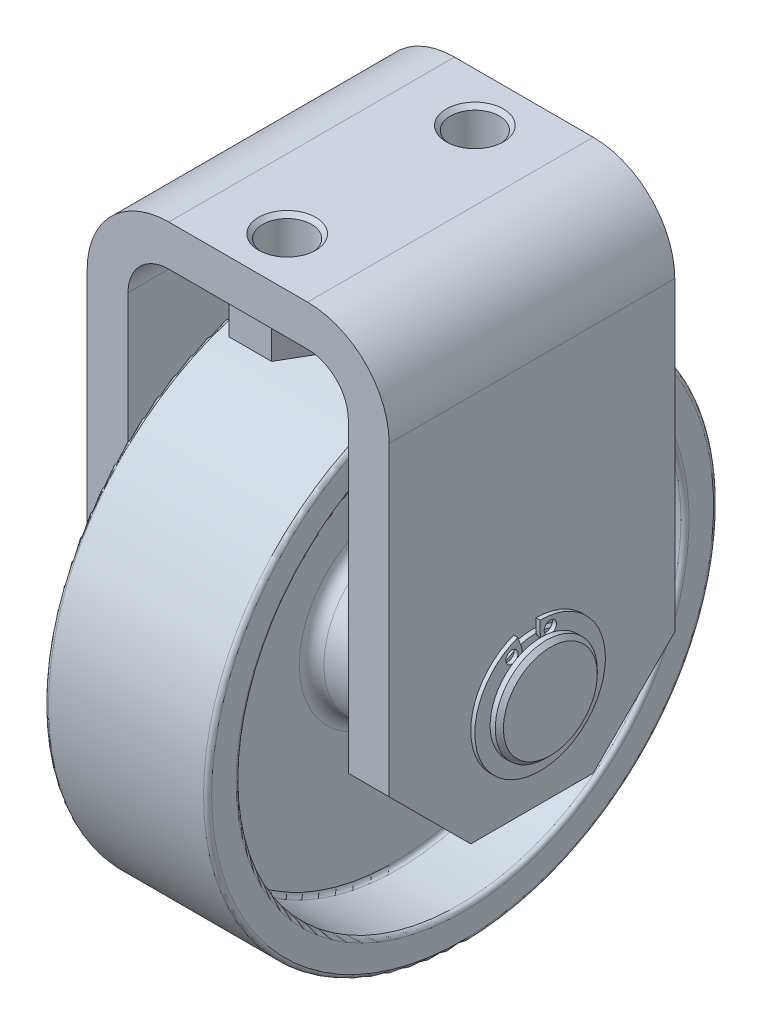
SolidWorks part; units mm, degrees
ref_plane "Front Plane" through (0, 0, 0) normal (0, 0, 1) x (1, 0, 0)
ref_plane "Top Plane" through (0, 0, 0) normal (0, 1, 0) x (1, 0, 0)
ref_plane "Right Plane" through (0, 0, 0) normal (1, 0, 0) x (0, 0, -1)
sketch "Sketch1" plane through (0, 0, 0) normal (0, 0, 1) x (1, 0, 0)
  line L0 (-43.3817, 0) -> (51.6188, 0) construction
  line L1 (55, 0) -> (-55, 0) construction
  line L2 (24, 13) -> (-24, 13)
  line L3 (0, -55) -> (0, 55) construction
  line L4 (-24, 13) -> (-24, 19)
  line L5 (-23, 20) -> (-6, 20)
  line L6 (-3, 23) -> (-3, 53.5)
  line L7 (-4, 54.5) -> (-19, 54.5)
  line L8 (-20, 55.5) -> (-20, 61.5)
  line L9 (-19, 62.5) -> (19, 62.5)
  line L10 (0, 62.5) -> (0, 13) construction
  line L11 (24, 13) -> (24, 19)
  line L12 (23, 20) -> (6, 20)
  line L13 (3, 23) -> (3, 53.5)
  line L14 (4, 54.5) -> (19, 54.5)
  line L15 (20, 55.5) -> (20, 61.5)
  arc A0 (-24, 19) -> (-23, 20) centre (-23, 19) cw
  arc A1 (-3, 53.5) -> (-4, 54.5) centre (-4, 53.5) ccw
  arc A2 (-19, 54.5) -> (-20, 55.5) centre (-19, 55.5) cw
  arc A3 (-20, 61.5) -> (-19, 62.5) centre (-19, 61.5) cw
  arc A4 (-6, 20) -> (-3, 23) centre (-6, 23) ccw
  arc A5 (24, 19) -> (23, 20) centre (23, 19) ccw
  arc A6 (6, 20) -> (3, 23) centre (6, 23) cw
  arc A7 (3, 53.5) -> (4, 54.5) centre (4, 53.5) cw
  arc A8 (19, 54.5) -> (20, 55.5) centre (19, 55.5) ccw
  arc A9 (20, 61.5) -> (19, 62.5) centre (19, 61.5) ccw
  point P22 (-20, 62.5)
  dimension "D8" = 1
  dimension "D9" = 3
  dimension "D1" = 40
  dimension "D2" = 109
  dimension "D3" = 125
  dimension "D4" = 20
  dimension "D5" = 3
  dimension "D6" = 24
  dimension "D7" = 13
revolve "Revolve1" add sketch "Sketch1" angle 360 about L0
sketch "Sketch2" plane through (0, 0, 0) normal (0, 0, 1) x (1, 0, 0)
  line L0 (-37, -25) -> (-37, 70)
  line L1 (-17, 90) -> (17, 90)
  line L2 (37, 70) -> (37, -25)
  line L3 (0, -68.75) -> (0, 68.75) construction
  line L4 (40.7, 0) -> (-40.7, 0) construction
  arc A0 (17, 90) -> (37, 70) centre (17, 70) cw
  arc A1 (-37, 70) -> (-17, 90) centre (-17, 70) cw
  point P2 (0, 90)
  point P11 (37, 90)
  point P14 (-37, 90)
  dimension "D4" = 20
  dimension "D1" = 115
  dimension "D2" = 74
  dimension "D3" = 90
extrude "Extrude-Thin1" add sketch "Sketch2" along normal mid plane 70 separate body thin
sketch "Sketch3" plane through (37, 0, 0) normal (1, 0, 0) x (0, 0, -1)
  circle A0 centre (0, 0) radius 13
  circle A1 centre (0, 0) radius 13 construction
extrude "Cut-Extrude1" cut sketch "Sketch3" against normal up to surface (74 mm away) up to face at (-37, 22.5, 0)
sketch "Sketch4" plane through (0, 0, 0) normal (1, 0, 0) x (0, 0, -1)
  circle A2 centre (0, 0) radius 12.5
  circle A3 centre (0, 0) radius 12.5
  dimension "D1" = 0.5
extrude "Boss-Extrude1" add sketch "Sketch4" along normal mid plane 83 separate body
chamfer "Chamfer1" distance 1 angle 45 2 edges at (-41.5, 0, -12.5) (41.5, 0, -12.5)
sketch "Sketch5" plane through (0, 0, 0) normal (0, 0, 1) x (1, 0, 0)
  line L0 (40.5, 12.5) -> (-40.5, 12.5) construction
  line L1 (-39.25, 12.5) -> (-37.75, 12.5)
  line L2 (-39.25, 12.5) -> (-39.25, 10.5)
  line L3 (-39.25, 10.5) -> (-37.75, 10.5)
  line L4 (-37.75, 12.5) -> (-37.75, 10.5)
  line L5 (-39.25, 12.5) -> (-37.75, 10.5) construction
  line L6 (-39.25, 10.5) -> (-37.75, 12.5) construction
  line L7 (-41.5, 11.5) -> (-41.5, -11.5) construction
  line L8 (0, 129.3642) -> (0, -93.634) construction
  line L9 (0, -68.75) -> (0, 68.75) construction
  line L10 (37.75, 12.5) -> (37.75, 10.5)
  line L11 (39.25, 12.5) -> (37.75, 12.5)
  line L12 (39.25, 12.5) -> (39.25, 10.5)
  line L13 (39.25, 10.5) -> (37.75, 10.5)
  point P4 (-38.5, 11.5)
  dimension "D1" = 3
  dimension "D2" = 1.5
  dimension "D3" = 2
revolve "Cut-Revolve1" cut sketch "Sketch5" angle 360
sketch "Sketch6" plane through (0, 0, 0) normal (0, 0, 1) x (1, 0, 0)
  line L0 (-37.75, 10.5) -> (-39.25, 10.5) construction
  line L1 (-39, 11) -> (-38, 11)
  line L2 (-39, 11) -> (-39, 16)
  line L3 (-39, 16) -> (-38, 16)
  line L4 (-38, 11) -> (-38, 16)
  line L5 (-39, 11) -> (-38, 16) construction
  line L6 (-39, 16) -> (-38, 11) construction
  line L7 (-39.25, -12.5) -> (-39.25, 12.5) construction
  point P4 (-38.5, 13.5)
  dimension "D1" = 5
  dimension "D2" = 0.5
  dimension "D3" = 1
  dimension "D4" = 0.25
revolve "Revolve2" add sketch "Sketch6" angle 340
sketch "Sketch7" plane through (-39, 0, 0) normal (-1, 0, 0) x (0, 0, 1)
  line L0 (0, 16) -> (0, 11) construction
  line L1 (5.4723, 15.0351) -> (3.7622, 10.3366) construction
  circle A0 centre (6.8866, 11.6114) radius 1.5
  circle A1 centre (-2.5, 13.2665) radius 1.5
  arc A4 (0, 13.5) -> (4.6173, 12.6859) centre (0, 0) ccw
  arc A5 (0, 13.5) -> (4.6173, 12.6859) centre (0, 0) ccw construction
  dimension "D1" = 2.5
  dimension "D3" = 3
  dimension "D2" = 2.5
  dimension "D4" = 2.5
extrude "Cut-Extrude2" cut sketch "Sketch7" against normal up to surface (1 mm away) up to face at (-38, -0.101, -0.0178)
fillet "Fillet1" radius 2.5 2 edges at (-38.5, 10.3366, 3.7622) (-38.5, 11, 0)
mirror "Mirror3" about plane through (0, 0, 0) normal (1, 0, 0) of bodies 107
sketch "Sketch8" plane through (0, 80, 0) normal (0, -1, 0) x (1, 0, 0)
  line L1 (5.1962, -32) -> (10.3923, -23)
  line L2 (10.3923, -23) -> (5.1962, -14)
  line L3 (5.1962, -14) -> (-5.1962, -14)
  line L4 (-5.1962, -14) -> (-10.3923, -23)
  line L5 (-10.3923, -23) -> (-5.1962, -32)
  line L6 (-5.1962, -32) -> (5.1962, -32)
  line L7 (5.1962, -55) -> (10.3923, -46) construction
  line L8 (10.3923, -46) -> (5.1962, -37) construction
  line L9 (5.1962, -37) -> (-5.1962, -37) construction
  line L10 (-5.1962, -37) -> (-10.3923, -46) construction
  line L11 (-10.3923, -46) -> (-5.1962, -55) construction
  line L12 (-5.1962, -55) -> (5.1962, -55) construction
  circle A0 centre (0, -23) radius 9 construction
  circle A1 centre (0, -46) radius 9 construction
  circle A2 centre (0, -23) radius 6
  circle A3 centre (0, -46) radius 6 construction
  point P23 (0, -14)
  dimension "D5" = 12
  dimension "D1" = 18
  dimension "D2" = 18
  dimension "D3" = 23
extrude "Boss-Extrude2" add sketch "Sketch8" along normal blind 10
sketch "Sketch9" [suppressed] plane through (0, 0, 0) normal (1, 0, 0) x (0, 0, -1)
  line L0 (32, 70) -> (35, 70)
  line L1 (-35, 70) -> (35, 70) construction
  line L2 (35, 70) -> (35, 71.7321)
  line L3 (35, 71.7321) -> (32, 70)
  dimension "D1" = 3
  dimension "D2" = 30
revolve "Cut-Revolve2" [suppressed] cut sketch "Sketch9" angle 360
chamfer "Chamfer2" [suppressed] distance 2 angle 45
sketch "Sketch10" plane through (0, 0, 0) normal (1, 0, 0) x (0, 0, -1)
  line L0 (32, 70) -> (35, 70)
  line L1 (-35, 70) -> (35, 70) construction
  line L2 (35, 70) -> (35, 71.7321)
  line L3 (35, 71.7321) -> (32, 70)
  dimension "D1" = 30
  dimension "D2" = 3
revolve "Cut-Revolve3" cut sketch "Sketch10" angle 360 about axis through (0, 70, -23) along (0, 1, 0)
chamfer "Chamfer3" distance 2 angle 45 6 edges at (-7.7942, 80, -27.5) (-7.7942, 80, -18.5) (0, 80, -14) (0, 80, -32) (7.7942, 80, -18.5) (7.7942, 80, -27.5)
sketch "Sketch11" plane through (0, 80, 0) normal (0, -1, 0) x (1, 0, 0)
  circle A0 centre (0, -23) radius 6 construction
  circle A2 centre (0, -23) radius 6
  circle A3 centre (0, -23) radius 6 construction
extrude "Cut-Extrude3" cut sketch "Sketch11" against normal up to surface (10 mm away) up to face at (0, 90, 0)
chamfer "Chamfer4" distance 1 angle 45 1 edges at (0, 70, -29)
chamfer "Chamfer5" distance 1 angle 45 1 edges at (0, 90, -17)
sketch "Sketch12" plane through (20, 0, 0) normal (1, 0, 0) x (0, 0, -1)
  line L0 (0, -55.5) -> (0, -62.5) construction
  circle A0 centre (0, 0) radius 55.5 construction
  circle A1 centre (0, 0) radius 62.5 construction
chamfer "Chamfer6" distance 20 angle 45 4 edges at (32, -25, 35) (32, -25, -35) (-32, -25, 35) (-32, -25, -35)
mirror "Mirror4" about plane through (0, 0, 0) normal (0, 0, 1) of "Boss-Extrude2"
mirror "Mirror6" about plane through (0, 0, 0) normal (0, 0, 1) of "Cut-Extrude3"
chamfer "Chamfer7" distance 1 angle 45 2 edges at (0, 70, 29) (0, 90, 29)
